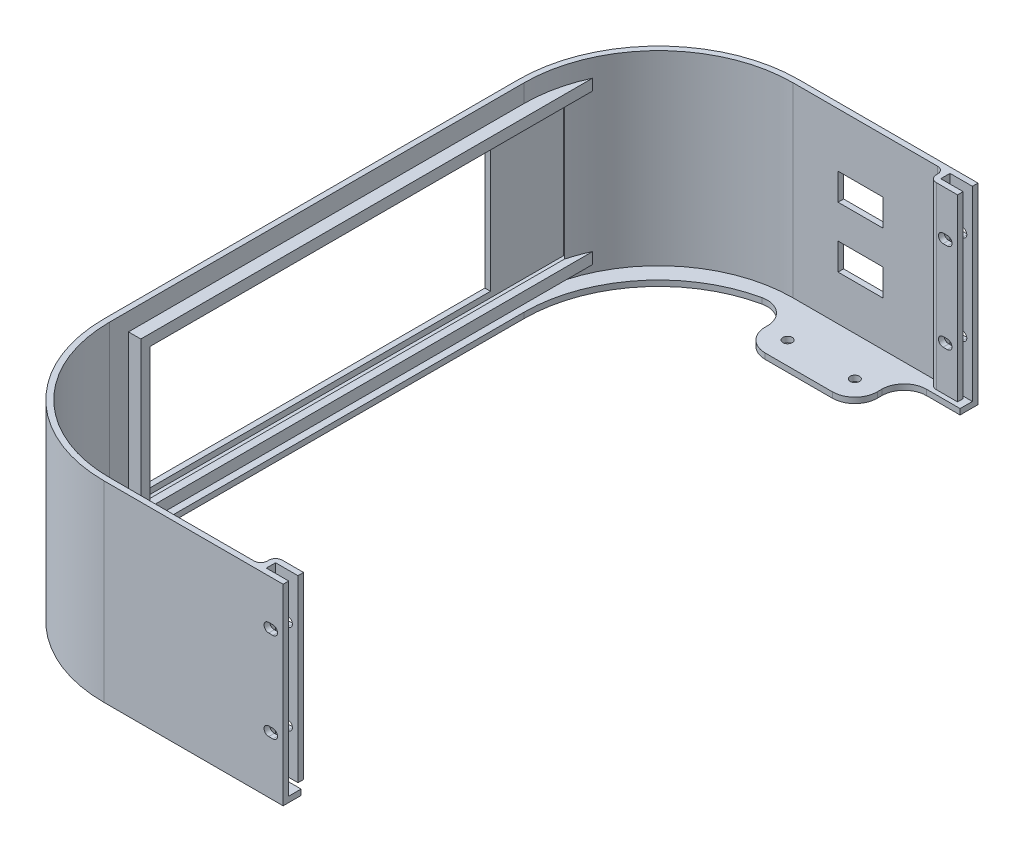
SolidWorks part; units mm, degrees
ref_plane "Alzado" through (0, 0, 0) normal (0, 0, 1) x (1, 0, 0)
ref_plane "Planta" through (0, 0, 0) normal (0, 1, 0) x (1, 0, 0)
ref_plane "Vista lateral" through (0, 0, 0) normal (1, 0, 0) x (0, 0, -1)
sketch "Croquis1" plane through (0, 0, 0) normal (0, 1, 0) x (1, 0, 0)
  line L8 (27.44, -152.5) -> (-100.06, -152.5)
  line L9 (-100.06, -152.5) -> (-100.06, 152.5)
  line L10 (-100.06, 152.5) -> (27.44, 152.5)
  line L11 (27.44, 152.5) -> (27.44, 155)
  line L12 (27.44, 155) -> (-102.56, 155)
  line L13 (-102.56, 155) -> (-102.56, -155)
  line L14 (-102.56, -155) -> (27.44, -155)
  line L15 (27.44, -155) -> (27.44, -152.5)
  line L17 (100, 152.44) -> (-100, 152.44) construction
  line L18 (100, 152.44) -> (100, -152.44) construction
  line L19 (100, -152.44) -> (-100, -152.44) construction
  line L20 (-100, 152.44) -> (-100, -152.44) construction
  line L21 (100, 152.44) -> (-100, -152.44) construction
  line L22 (100, -152.44) -> (-100, 152.44) construction
  point P1 (0, 0)
  dimension "D8" = 2.5
  dimension "D9" = 2.5
  dimension "D1" = 304.88
  dimension "D3" = 0.06
  dimension "D4" = 0.06
  dimension "D5" = 0.06
  dimension "D6" = 200
  dimension "D2" = 130
extrude "Saliente-Extruir1" add sketch "Croquis1" along normal blind 83.12
fillet "Redondeo1" radius 60 2 edges at (-100.06, 41.56, 152.5) (-100.06, 41.56, -152.5)
sketch "Croquis2" plane through (0, 0, 0) normal (0, -1, 0) x (1, 0, 0)
  line L0 (27.44, -155) -> (-102.56, -155) construction
  line L1 (-102.56, -155) -> (-102.56, 155) construction
  line L2 (-102.56, 155) -> (27.44, 155) construction
  line L3 (27.44, -155) -> (-102.56, -155)
  line L4 (-102.56, -155) -> (-102.56, 155)
  line L5 (-102.56, 155) -> (27.44, 155)
  line L6 (27.44, 155) -> (27.44, 147)
  line L7 (27.44, 147) -> (-34.5597, 147)
  line L8 (-94.5597, 87) -> (-94.5597, -87)
  line L9 (-34.5597, -147) -> (27.44, -147)
  line L10 (27.44, -147) -> (27.44, -155)
  arc A6 (-94.5597, -87) -> (-34.5597, -147) centre (-34.5597, -87) ccw
  arc A7 (-34.5597, 147) -> (-94.5597, 87) centre (-34.5597, 87) ccw
  point P7 (0, 0)
  point P9 (0, 0)
  point P16 (-79.4736, 81.5697)
  point P19 (-84.56, 88.56)
  dimension "D1" = 60
  dimension "D2" = 8
  dimension "D5" = 8.0003
extrude "Saliente-Extruir2" add sketch "Croquis2" along normal blind 2.5
ref_plane "Plano1" through (0, 3.12, 0) normal (0, 1, 0) x (1, 0, 0)
sketch "Croquis5" plane through (0, 3.12, 0) normal (0, 1, 0) x (1, 0, 0)
  line L0 (27.44, -152.5) -> (-40.06, -152.5) construction
  line L1 (-100.06, 155) -> (-94.5597, 155)
  line L2 (-100.06, 155) -> (-100.06, -152.5)
  line L3 (-100.06, -152.5) -> (-94.5597, -152.5)
  line L4 (-94.5597, 155) -> (-94.5597, -152.5)
  line L5 (-100.06, 155) -> (-94.5597, -152.5) construction
  line L6 (-100.06, -152.5) -> (-94.5597, 155) construction
  line L7 (-94.5597, 87) -> (-94.5597, -87) construction
  line L8 (-100.06, -92.5) -> (-100.06, 92.5) construction
  line L9 (27.44, 155) -> (-102.56, 155) construction
  point P4 (-97.3099, 1.25)
  point P5 (0, 0)
extrude "Saliente-Extruir4" add sketch "Croquis5" along normal blind 5
sketch "Croquis6" plane through (0, 0, -155) normal (0, 0, -1) x (-1, 0, 0)
  line L0 (102.56, 83.12) -> (102.56, -2.5) construction
  line L1 (100.06, 7.5) -> (97.94, 7.5)
  line L2 (100.06, 7.5) -> (100.06, 72.62)
  line L3 (100.06, 72.62) -> (97.94, 72.62)
  line L4 (97.94, 7.5) -> (97.94, 72.62)
  line L5 (100.06, 7.5) -> (97.94, 72.62) construction
  line L6 (100.06, 72.62) -> (97.94, 7.5) construction
  line L9 (102.56, -2.5) -> (-27.44, -2.5) construction
  point P4 (99, 40.06)
  dimension "D1" = 2.5
  dimension "D2" = 2.12
  dimension "D4" = 65.12
  dimension "D3" = 10
extrude "Cortar-Extruir2" cut sketch "Croquis6" against normal blind 235
sketch "Croquis7" plane through (-102.56, 0, 0) normal (-1, 0, 0) x (0, 0, 1)
  line L1 (-77.5, 70.06) -> (77.5, 70.06)
  line L2 (-77.5, 70.06) -> (-77.5, 10.06)
  line L3 (-77.5, 10.06) -> (77.5, 10.06)
  line L4 (77.5, 70.06) -> (77.5, 10.06)
  line L5 (-77.5, 70.06) -> (77.5, 10.06) construction
  line L6 (-77.5, 10.06) -> (77.5, 70.06) construction
  point P0 (0, 40.06)
  dimension "D2" = 60
  dimension "D3" = 155
  dimension "D1" = 2.56
extrude "Cortar-Extruir3" cut sketch "Croquis7" against normal blind 3
sketch "Croquis8" plane through (-100.06, 0, 0) normal (1, 0, 0) x (0, 0, -1)
  line L1 (-84, 74.12) -> (-80, 74.12)
  line L2 (-84, 74.12) -> (-84, 8.12)
  line L3 (-84, 8.12) -> (-80, 8.12)
  line L4 (-80, 74.12) -> (-80, 8.12)
  line L5 (-84, 74.12) -> (-80, 8.12) construction
  line L6 (-84, 8.12) -> (-80, 74.12) construction
  point P0 (-82, 41.12)
  dimension "D1" = 66
  dimension "D2" = 4
extrude "Saliente-Extruir5" add sketch "Croquis8" along normal up to surface (5.5003 mm away) up to face at (-94.5597, 5.62, 0)
sketch "Croquis9" plane through (0, 0, -152.5) normal (0, 0, 1) x (1, 0, 0)
  line L0 (-100.06, 72.62) -> (-97.94, 72.62)
  line L1 (-97.94, 72.62) -> (-97.94, 70.17)
  line L2 (-97.94, 70.17) -> (-94.5597, 70.17)
  line L3 (-94.5597, 70.17) -> (-94.5597, 75.12)
  line L4 (-94.5597, 75.12) -> (-100.06, 75.12)
  line L6 (-100.06, 75.12) -> (-100.06, 72.62)
  line L7 (-97.94, 72.62) -> (-97.94, 8.12) construction
  line L9 (-94.5597, 8.12) -> (-97.94, 8.12) construction
  point P2 (-100.06, 76.3079)
  point P8 (0, 0)
  dimension "D1" = 2.45
  dimension "D2" = 2.5
extrude "Saliente-Extruir9" add sketch "Croquis9" along normal up to surface (236.5 mm away) up to face at (-97.3099, 41.12, 84)
sketch "Croquis11" plane through (0, 0, -155) normal (0, 0, -1) x (-1, 0, 0)
  line L1 (0, 59) -> (20, 59)
  line L2 (0, 59) -> (0, 47)
  line L3 (0, 47) -> (20, 47)
  line L4 (20, 59) -> (20, 47)
  line L5 (0, 59) -> (20, 47) construction
  line L6 (0, 47) -> (20, 59) construction
  line L7 (0, 32) -> (20, 32)
  line L8 (0, 32) -> (0, 20)
  line L9 (0, 20) -> (20, 20)
  line L10 (20, 32) -> (20, 20)
  line L11 (0, 32) -> (20, 20) construction
  line L12 (0, 20) -> (20, 32) construction
  point P0 (10, 53)
  point P5 (10, 26)
  dimension "D1" = 12
  dimension "D2" = 20
  dimension "D3" = 10
  dimension "D4" = 20
  dimension "D5" = 15
extrude "Cortar-Extruir4" cut sketch "Croquis11" against normal blind 2.5
sketch "Croquis12" plane through (0, 83.12, 0) normal (0, 1, 0) x (1, 0, 0)
  line L0 (-102.56, -92.5) -> (-102.56, -155)
  line L1 (-102.56, -155) -> (-40.06, -155)
  line L2 (-102.56, 92.5) -> (-102.56, 155)
  line L3 (-102.56, 155) -> (-40.06, 155)
  arc A0 (-40.06, 155) -> (-102.56, 92.5) centre (-40.06, 92.5) ccw
  arc A1 (-102.56, -92.5) -> (-40.06, -155) centre (-40.06, -92.5) ccw
  arc A2 (-100.06, -92.5) -> (-40.06, -152.5) centre (-40.06, -92.5) ccw construction
  arc A3 (-40.06, 152.5) -> (-100.06, 92.5) centre (-40.06, 92.5) ccw construction
  dimension "D1" = 2.5
  dimension "D2" = 2.5
extrude "Cortar-Extruir5" cut sketch "Croquis12" against normal through all
sketch "Croquis13" plane through (0, -2.5, 0) normal (0, -1, 0) x (1, 0, 0)
  line L0 (-40.06, -155) -> (27.44, -155) construction
  line L1 (-35, -155) -> (15, -155)
  line L2 (-35, -155) -> (-35, -125)
  line L3 (-35, -125) -> (15, -125)
  line L4 (15, -155) -> (15, -125)
  line L5 (-35, -155) -> (15, -125) construction
  line L6 (-35, -125) -> (15, -155) construction
  line L7 (27.44, 155) -> (-40.06, 155) construction
  line L8 (-35, 155) -> (15, 155)
  line L9 (-35, 155) -> (-35, 125)
  line L10 (-35, 125) -> (15, 125)
  line L11 (15, 155) -> (15, 125)
  line L12 (-35, 155) -> (15, 125) construction
  line L13 (-35, 125) -> (15, 155) construction
  line L17 (-20, -152.5) -> (0, -152.5) construction
  circle A0 centre (-25, 135) radius 2.06
  circle A1 centre (5, 135) radius 2.06
  circle A2 centre (-25, -135) radius 2.06
  circle A3 centre (5, -135) radius 2.06
  point P4 (-10, -140)
  point P11 (-10, 140)
  point P22 (90.708, 135)
  point P23 (0, 0)
  point P24 (0, 0)
  point P25 (0, 0)
  point P27 (20.146, -119.3575)
  point P28 (42.2155, -125.7814)
  point P31 (-10, -152.5)
  dimension "D3" = 10
  dimension "D4" = 4.12
  dimension "D5" = 10
  dimension "D6" = 10
  dimension "D7" = 10
  dimension "D1" = 0
  dimension "D2" = 50
  dimension "D8" = 30
extrude "Saliente-Extruir10" add sketch "Croquis13" against normal up to surface (2.5 mm away) up to face at (-39.8687, 0, 0)
fillet "Redondeo2" radius 10 8 edges at (15, -1.25, 125) (-35, -1.25, 125) (15, -1.25, 147) (15, -1.25, -147) (15, -1.25, -125) (-35, -1.25, -125) (-35, -1.25, 146.9984) (-35, -1.25, -146.9984)
sketch "Croquis14" plane through (27.44, 0, 0) normal (1, 0, 0) x (0, 0, -1)
  line L0 (-155, 83.12) -> (-145.88, 83.12)
  line L1 (-145.88, 83.12) -> (-145.88, 3.12)
  line L2 (-145.88, 3.12) -> (-152.5, 3.12)
  line L3 (-152.5, 3.12) -> (-152.5, 0)
  line L4 (-152.5, 0) -> (-147, 0)
  line L5 (-147, 0) -> (-147, -2.5)
  line L6 (-155, 83.12) -> (-155, -2.5)
  line L7 (-155, -2.5) -> (-147, -2.5)
  line L8 (-147, -2.5) -> (-147, 0)
  line L9 (-147, 0) -> (-152.5, 0)
  line L10 (-152.5, 0) -> (-152.5, 83.12)
  line L11 (-152.5, 83.12) -> (-155, 83.12)
  line L12 (-155, 83.12) -> (-155, -2.5) construction
  line L13 (-155, -2.5) -> (-147, -2.5) construction
  line L14 (-147, -2.5) -> (-147, 0) construction
  line L15 (-147, 0) -> (-152.5, 0) construction
  line L16 (-152.5, 0) -> (-152.5, 83.12) construction
  line L17 (-152.5, 83.12) -> (-155, 83.12) construction
  line L18 (152.5, 83.12) -> (152.5, 0)
  line L19 (152.5, 0) -> (147, 0)
  line L20 (147, 0) -> (147, -2.5)
  line L21 (147, -2.5) -> (155, -2.5)
  line L22 (155, -2.5) -> (155, 83.12)
  line L23 (155, 83.12) -> (152.5, 83.12)
  line L24 (152.5, 83.12) -> (152.5, 0) construction
  line L25 (152.5, 0) -> (147, 0) construction
  line L26 (147, 0) -> (147, -2.5) construction
  line L27 (147, -2.5) -> (155, -2.5) construction
  line L28 (155, -2.5) -> (155, 83.12) construction
  line L29 (155, 83.12) -> (152.5, 83.12) construction
  line L30 (-147, -2.5) -> (-155, -2.5)
  line L31 (-155, -2.5) -> (-155, 83.12)
  line L32 (145.88, 83.12) -> (155, 83.12)
  line L33 (155, 83.12) -> (155, -2.5)
  line L34 (155, -2.5) -> (147, -2.5)
  line L35 (147, -2.5) -> (147, 0)
  line L36 (147, 0) -> (152.5, 0)
  line L37 (152.5, 0) -> (152.5, 3.12)
  line L38 (152.5, 3.12) -> (145.88, 3.12)
  line L39 (145.88, 3.12) -> (145.88, 83.12)
  point P23 (-113.5528, 47.4203)
  dimension "D3" = 9.12
  dimension "D4" = 3.12
extrude "Saliente-Extruir11" add sketch "Croquis14" along normal blind 12.5
sketch "Croquis15" plane through (0, 83.12, 0) normal (0, 1, 0) x (1, 0, 0)
  line L0 (39.94, 155) -> (39.94, 145.88) construction
  line L1 (39.94, 152.5) -> (29.94, 152.5)
  line L2 (39.94, 152.5) -> (39.94, 148.38)
  line L3 (39.94, 148.38) -> (29.94, 148.38)
  line L4 (29.94, 152.5) -> (29.94, 148.38)
  line L5 (39.94, 152.5) -> (29.94, 148.38) construction
  line L6 (39.94, 148.38) -> (29.94, 152.5) construction
  line L7 (39.94, -145.88) -> (39.94, -155) construction
  line L8 (39.94, -148.38) -> (29.94, -148.38)
  line L9 (39.94, -148.38) -> (39.94, -152.5)
  line L10 (39.94, -152.5) -> (29.94, -152.5)
  line L11 (29.94, -148.38) -> (29.94, -152.5)
  line L12 (39.94, -148.38) -> (29.94, -152.5) construction
  line L13 (39.94, -152.5) -> (29.94, -148.38) construction
  line L14 (39.94, -155) -> (-40.06, -155) construction
  line L15 (39.94, 155) -> (-40.06, 155) construction
  line L17 (27.44, -145.88) -> (27.44, -152.5) construction
  point P4 (34.94, 150.44)
  point P11 (34.94, -150.44)
  dimension "D1" = 4.12
  dimension "D2" = 2.5
  dimension "D4" = 2.5
  dimension "D3" = 2.5
extrude "Cortar-Extruir6" cut sketch "Croquis15" against normal up to next
fillet "Redondeo3" radius 3 4 edges at (27.44, 43.12, 152.5) (27.44, 43.12, -152.5) (27.44, 43.12, -145.88) (27.44, 43.12, 145.88)
sketch "Croquis16" plane through (0, 0, -145.88) normal (0, 0, 1) x (1, 0, 0)
  line L0 (33.5, 63.12) -> (35.38, 63.12) construction
  line L1 (33.5, 65.18) -> (35.38, 65.18)
  line L2 (33.5, 61.06) -> (35.38, 61.06)
  line L3 (33.5, 23.12) -> (35.38, 23.12) construction
  line L4 (33.5, 25.18) -> (35.38, 25.18)
  line L5 (39.94, 83.12) -> (39.94, 3.12) construction
  line L6 (39.94, 83.12) -> (30.44, 83.12) construction
  line L7 (33.5, 21.06) -> (35.38, 21.06)
  arc A0 (33.5, 65.18) -> (33.5, 61.06) centre (33.5, 63.12) ccw
  arc A1 (35.38, 61.06) -> (35.38, 65.18) centre (35.38, 63.12) ccw
  arc A2 (33.5, 25.18) -> (33.5, 21.06) centre (33.5, 23.12) ccw
  arc A3 (35.38, 21.06) -> (35.38, 25.18) centre (35.38, 23.12) ccw
  point P2 (34.44, 63.12)
  point P10 (34.44, 23.12)
  point P12 (37.44, 63.12)
  point P15 (31.44, 63.12)
  dimension "D1" = 2.5
  dimension "D2" = 4.12
  dimension "D3" = 6
  dimension "D4" = 20
  dimension "D5" = 2
extrude "Cortar-Extruir7" cut sketch "Croquis16" against normal through all and the other way through all
equation "\"venesta\"= 4'grosor de la venesta"
equation "\"policarbonato\"= 4'grosor del policarbonato"
equation "\"carton_trupan\"= 3'grosor del carton trupan caso laser"
equation "\"ancho_tot\"= 310'ancho tot sin llantas"
equation "\"largo_tot\"= 400'largo tot sin camera"
equation "\"alto_estimado\"= 300'alto estimado sin lidar"
equation "\"altoparaqpaselabotella\"= 75'alto estimado para que encaje la botella"
equation "\"alturaruedaloca\"= 22"
equation "\"anchoruedaloca\"= 35"
equation "\"anchopiso1motorybaterias\"= 150"
equation "\"dist-pisorampa\"= 5"
equation "\"anchoultimopiso\"= 170"
equation "\"paredtrasera\"= 100"
equation "\"agarradorcanasta\"= 275'recolector"
equation "\"alturapiso1y2\"= 80"
equation "\"alturapiso2y3\"= 80"
equation "\"GROSOR_PARED_IMPRESION\"= 2.5"
equation "\"TOLERANCIA\"= 0.06"
equation "\"D8@Croquis1\"=\"GROSOR_PARED_IMPRESION\""
equation "\"D9@Croquis1\"=\"GROSOR_PARED_IMPRESION\""
equation "\"apertura\"= 70"
equation "\"D1@Saliente-Extruir2\"=\"GROSOR_PARED_IMPRESION\""
equation "\"D1@Saliente-Extruir1\"=\"TOLERANCIA\"+\"carton_trupan\"+\"TOLERANCIA\"+\"alturapiso1y2\""
equation "\"D1@Croquis6\"=\"GROSOR_PARED_IMPRESION\""
equation "\"D2@Croquis6\"=\"acrilico\"+\"TOLERANCIA\"*2"
equation "\"D1@Cortar-Extruir2\"=\"ancho_tot\"-75"
equation "\"acrilico\"= 2"
equation "\"D3@Croquis1\"=\"TOLERANCIA\""
equation "\"D4@Croquis1\"=\"TOLERANCIA\""
equation "\"D4@Croquis6\"=\"TOLERANCIA\"+65+\"TOLERANCIA\""
equation "\"D1@Croquis7\"=2.5+0.06"
equation "\"D4@Croquis13\"=4+\"TOLERANCIA\"*2"
equation "\"D4@Croquis14\"=\"TOLERANCIA\"+\"carton_trupan\"+\"TOLERANCIA\""
equation "\"D3@Croquis14\"=\"GROSOR_PARED_IMPRESION\"+\"TOLERANCIA\"+\"policarbonato\"+\"TOLERANCIA\"+\"GROSOR_PARED_IMPRESION\""
equation "\"D1@Croquis15\"=\"TOLERANCIA\"+\"policarbonato\"+\"TOLERANCIA\""
equation "\"D2@Croquis15\"=\"GROSOR_PARED_IMPRESION\""
equation "\"D4@Croquis15\"=\"GROSOR_PARED_IMPRESION\""
equation "\"D1@Saliente-Extruir11\"=\"GROSOR_PARED_IMPRESION\"+10"
equation "\"D3@Croquis15\"=\"GROSOR_PARED_IMPRESION\""
equation "\"D2@Croquis16\"=4+\"TOLERANCIA\"*2"
